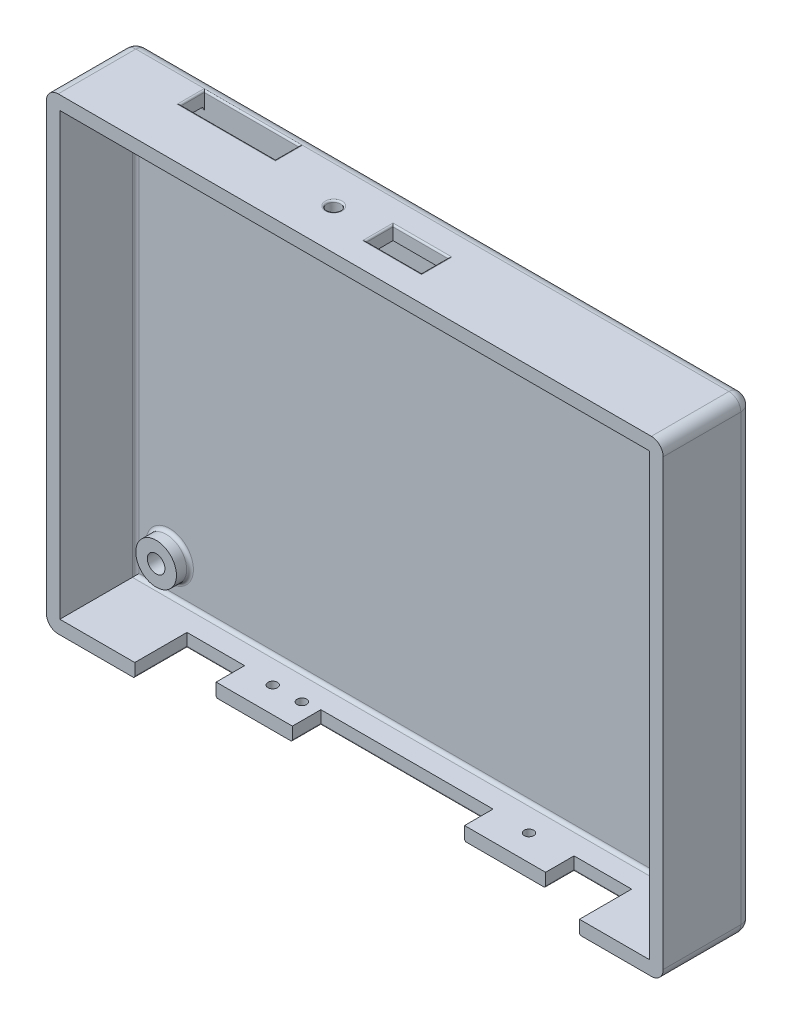
SolidWorks part; units mm, degrees
ref_plane "Front Plane" through (0, 0, 0) normal (0, 0, 1) x (1, 0, 0)
ref_plane "Top Plane" through (0, 0, 0) normal (0, 1, 0) x (1, 0, 0)
ref_plane "Right Plane" through (0, 0, 0) normal (1, 0, 0) x (0, 0, -1)
sketch "Sketch1" plane through (0, 0, 0) normal (0, 0, 1) x (1, 0, 0)
  line L1 (0, 0) -> (91, 0)
  line L2 (0, 0) -> (0, 69)
  line L3 (0, 69) -> (91, 69)
  line L4 (91, 0) -> (91, 69)
extrude "Boss-Extrude1" add sketch "Sketch1" along normal blind 13.2
shell "Shell2" thickness 2
sketch "Sketch2" plane through (0, 0, 2) normal (0, 0, 1) x (1, 0, 0)
  line L1 (2, 67) -> (7, 67)
  line L2 (2, 67) -> (2, 62)
  line L3 (2, 62) -> (7, 62)
  line L4 (7, 67) -> (7, 62)
  line L5 (89, 67) -> (84, 67)
  line L6 (89, 67) -> (89, 62)
  line L7 (89, 62) -> (84, 62)
  line L8 (84, 67) -> (84, 62)
  line L9 (89, 2) -> (84, 2)
  line L10 (89, 2) -> (89, 7)
  line L11 (89, 7) -> (84, 7)
  line L12 (84, 2) -> (84, 7)
  line L13 (2, 2) -> (7, 2)
  line L14 (2, 2) -> (2, 7)
  line L15 (2, 7) -> (7, 7)
  line L16 (7, 2) -> (7, 7)
  circle A0 centre (7, 62) radius 3
  circle A1 centre (84, 62) radius 3
  circle A2 centre (84, 7) radius 3
  circle A3 centre (7, 7) radius 3
extrude "Boss-Extrude2" add sketch "Sketch2" along normal blind 2 contours L16 A3 L15 | L15 A3 L16 | L3 A0 L4 | L4 A0 L3 | L8 A1 L7 | L7 A1 L8 | L11 A2 L12 | L12 A2 L11
sketch "Sketch3" plane through (0, 0, 4) normal (0, 0, 1) x (1, 0, 0)
  circle A0 centre (7, 62) radius 1.3
  circle A1 centre (84, 62) radius 1.3
  circle A2 centre (84, 7) radius 1.3
  circle A3 centre (7, 7) radius 1.3
extrude "Cut-Extrude1" cut sketch "Sketch3" against normal blind 4
sketch "Sketch5" plane through (0, 0, 0) normal (0, 0, -1) x (-1, 0, 0)
  circle A0 centre (-84, 62) radius 2.1
  circle A1 centre (-7, 62) radius 2.1
  circle A2 centre (-7, 7) radius 2.1
  circle A3 centre (-84, 7) radius 2.1
extrude "Cut-Extrude2" cut sketch "Sketch5" against normal blind 1.7
sketch "Sketch6" plane through (0, 0, 0) normal (0, -1, 0) x (-1, 0, 0)
  line L1 (-13.05, -5.5) -> (-21.65, -5.5)
  line L2 (-13.05, -5.5) -> (-13.05, -13.2)
  line L3 (-13.05, -13.2) -> (-21.65, -13.2)
  line L4 (-21.65, -5.5) -> (-21.65, -13.2)
  line L5 (-70.15, -5.5) -> (-78.65, -5.5)
  line L6 (-70.15, -5.5) -> (-70.15, -13.2)
  line L7 (-70.15, -13.2) -> (-78.65, -13.2)
  line L8 (-78.65, -5.5) -> (-78.65, -13.2)
  line L9 (-32.8, -5.5) -> (-58.2, -5.5)
  line L10 (-32.8, -5.5) -> (-32.8, -13.2)
  line L11 (-32.8, -13.2) -> (-58.2, -13.2)
  line L12 (-58.2, -5.5) -> (-58.2, -13.2)
sketch "Sketch7" plane through (0, 0, 0) normal (0, -1, 0) x (-1, 0, 0)
  circle A0 centre (-26.1, -5.9) radius 0.7
  circle A1 centre (-30.4, -5.9) radius 0.7
  circle A2 centre (-63.9, -5.9) radius 0.7
extrude "Cut-Extrude4" cut sketch "Sketch7" against normal blind 2
sketch "Sketch8" plane through (0, 69, 0) normal (0, 1, 0) x (1, 0, 0)
  line L1 (12.1, -2) -> (26.1, -2)
  line L2 (12.1, -2) -> (12.1, -5.5)
  line L3 (12.1, -5.5) -> (26.1, -5.5)
  line L4 (26.1, -2) -> (26.1, -5.5)
  line L5 (43.2, -5.25) -> (51.4, -5.25)
  line L6 (43.2, -5.25) -> (43.2, -9.25)
  line L7 (43.2, -9.25) -> (51.4, -9.25)
  line L8 (51.4, -5.25) -> (51.4, -9.25)
sketch "Sketch9" plane through (0, 69, 0) normal (0, 1, 0) x (1, 0, 0)
  circle A0 centre (36.4, -7.2) radius 1
extrude "Cut-Extrude6" cut sketch "Sketch9" against normal blind 2
sketch "Sketch12" plane through (0, 0, 0) normal (0, 0, -1) x (-1, 0, 0)
  line L1 (-28.5, 20.5) -> (-62.5, 20.5)
  line L2 (-28.5, 20.5) -> (-28.5, 48.5)
  line L3 (-28.5, 48.5) -> (-62.5, 48.5)
  line L4 (-62.5, 20.5) -> (-62.5, 48.5)
extrude "Cut-Extrude9" cut sketch "Sketch12" against normal blind 0.2
fillet "Fillet5" radius 0.2 4 edges at (45.5, 48.5, 0) (62.5, 34.5, 0) (28.5, 34.5, 0) (45.5, 20.5, 0)
fillet "Fillet6" radius 1.75 8 edges at (91, 0, 6.6) (91, 34.5, 0) (91, 69, 6.6) (45.5, 69, 0) (0, 69, 6.6) (0, 34.5, 0) (0, 0, 6.6) (45.5, 0, 0)
extrude "Cut-Extrude10" cut sketch "Sketch6" against normal blind 2
sketch "Sketch14" plane through (0, 0, 0) normal (0, -1, 0) x (-1, 0, 0)
  line L0 (-32.8, -13.2) -> (-32.8, -5.5) construction
  line L1 (-21.65, -13.2) -> (-32.8, -13.2)
  line L2 (-21.65, -13.2) -> (-21.65, -9.7)
  line L3 (-21.65, -9.7) -> (-32.8, -9.7)
  line L4 (-32.8, -13.2) -> (-32.8, -9.7)
  line L5 (-70.15, -13.2) -> (-70.15, -5.5) construction
  line L6 (-58.2, -13.2) -> (-70.15, -13.2)
  line L7 (-58.2, -13.2) -> (-58.2, -9.7)
  line L8 (-58.2, -9.7) -> (-70.15, -9.7)
  line L9 (-70.15, -13.2) -> (-70.15, -9.7)
  point P14 (0, 0)
  point P15 (0, 0)
extrude "Cut-Extrude12" cut sketch "Sketch8" against normal blind 2
sketch "Sketch16" plane through (0, 0, 0) normal (0, -1, 0) x (-1, 0, 0)
  line L0 (-89, -13.2) -> (-2, -13.2) construction
  line L1 (-21.65, -5.5) -> (-21.55, -5.5)
  line L2 (-21.65, -5.5) -> (-21.65, -13.2)
  line L3 (-21.65, -13.2) -> (-21.55, -13.2)
  line L4 (-21.55, -5.5) -> (-21.55, -13.2)
extrude "Boss-Extrude3" add sketch "Sketch16" against normal blind 2
extrude "Cut-Extrude13" cut sketch "Sketch14" against normal blind 2
sketch "Sketch17" plane through (0, 0, 0) normal (0, -1, 0) x (-1, 0, 0)
  line L1 (-21.65, -9.7) -> (-21.55, -9.7)
  line L2 (-21.65, -9.7) -> (-21.65, -13.2)
  line L3 (-21.65, -13.2) -> (-21.55, -13.2)
  line L4 (-21.55, -9.7) -> (-21.55, -13.2)
extrude "Cut-Extrude14" cut sketch "Sketch17" against normal blind 2
fillet "Fillet8" radius 0.25 21 edges at (51.4, 69, 7.25) (47.3, 69, 5.25) (47.3, 69, 9.25) (43.2, 69, 7.25) (36.4, 69, 8.2) (26.1, 69, 3.75) (19.1, 69, 5.5) (12.1, 69, 3.75) (19.1, 69, 2) (70.15, 0, 7.6) (74.4, 0, 5.5) (78.65, 0, 9.35) (58.2, 0, 7.6) (63.9, 0, 5.2) (32.8, 0, 7.6) (45.5, 0, 5.5) (13.05, 0, 9.35) (30.4, 0, 5.2) (26.1, 0, 5.2) (17.3, 0, 5.5) (21.55, 0, 7.6)
fillet "Fillet9" radius 0.5 9 edges at (2, 34.5, 2) (45.5, 2, 2) (89, 34.5, 2) (57.55, 67, 2) (7.05, 67, 2) (4, 7, 2) (4, 62, 2) (81, 62, 2) (81, 7, 2)
